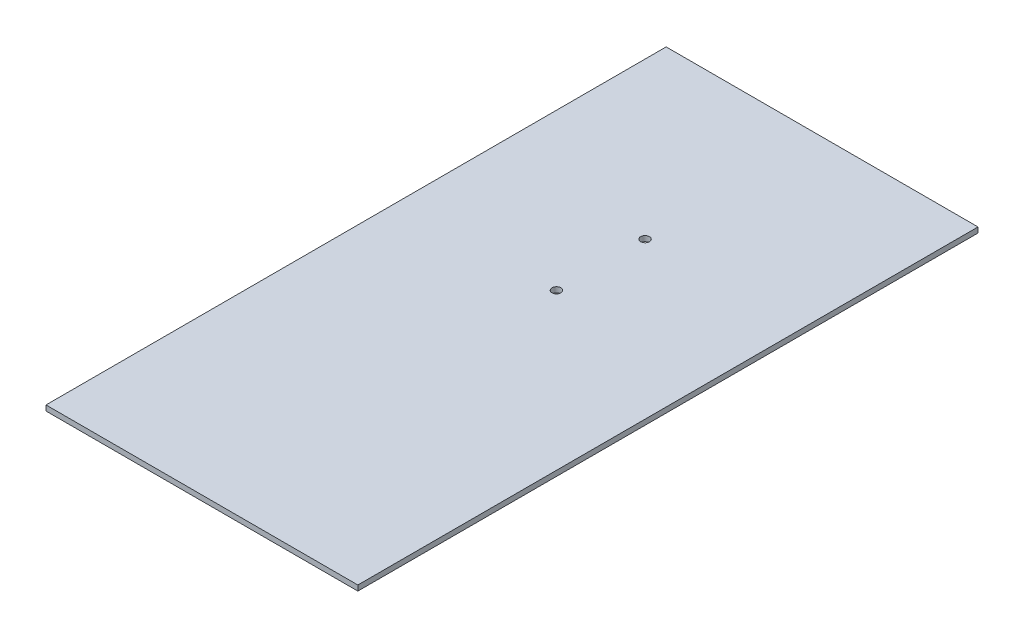
SolidWorks part; units mm, degrees
ref_plane "Front Plane" through (0, 0, 0) normal (0, 0, 1) x (1, 0, 0)
ref_plane "Top Plane" through (0, 0, 0) normal (0, 1, 0) x (1, 0, 0)
ref_plane "Right Plane" through (0, 0, 0) normal (1, 0, 0) x (0, 0, -1)
sketch "Sketch1" plane through (0, 0, 0) normal (0, 1, 0) x (1, 0, 0)
  line L1 (0, 0) -> (176, 0)
  line L2 (0, 0) -> (0, 350)
  line L3 (0, 350) -> (176, 350)
  line L4 (176, 0) -> (176, 350)
  dimension "D1" = 350
  dimension "D2" = 176
extrude "Boss-Extrude1" add sketch "Sketch1" along normal blind 3
hole_wizard "Ø5.0mm Dowel Hole1" positions "Sketch2" profile "Sketch3" hole size "Ø5.0" standard "ANSI Metric" end condition up to next
sketch "Sketch2" plane through (0, 0, 0) normal (0, -1, 0) x (-1, 0, 0)
  point P0 (-88.0169, 250.06)
  point P3 (-88.0169, 200.06)
sketch "Sketch3" plane through (88.0169, 0, -250.06) normal (1, 0, 0) x (0, 0, -1)
  line L0 (0, 0) -> (0, 3)
  line L1 (0, 3) -> (2.5, 3)
  line L2 (2.5, 3) -> (2.5, 0)
  line L5 (2.5, 0) -> (0, 0)
  line L11 (0, -6.35) -> (0, 107.95) construction
  dimension "Thru Hole Dia." = 5
  dimension "Thru Hole Depth" = 3
